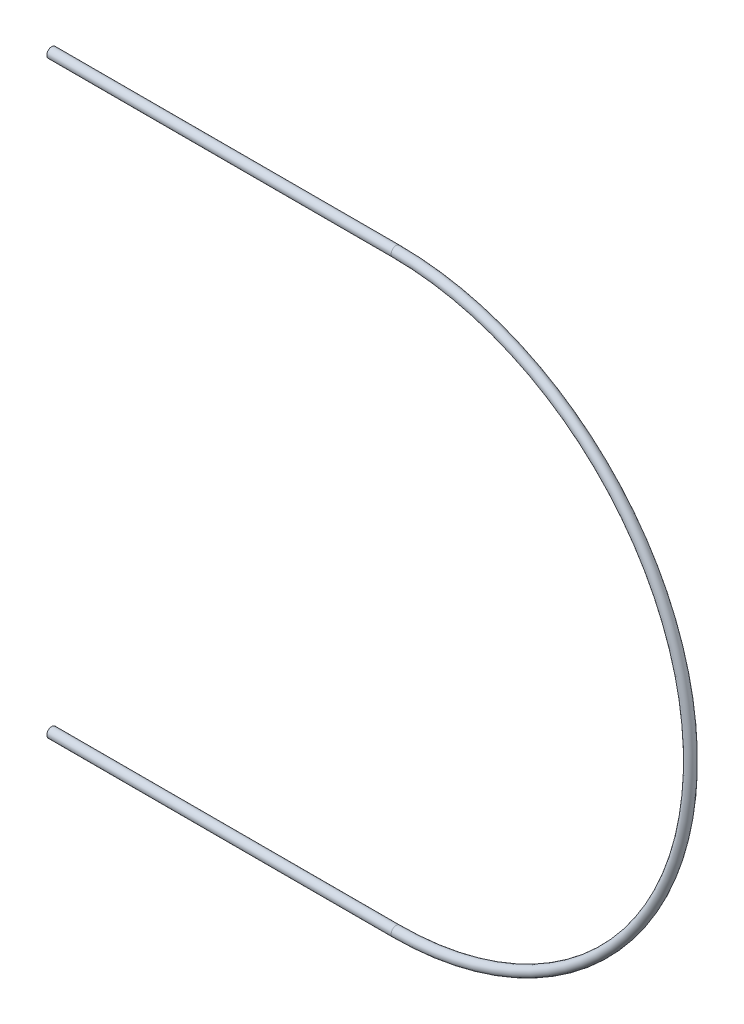
SolidWorks part; units mm, degrees
material "SA-193 B7"
ref_plane "Front Plane" through (0, 0, 0) normal (0, 0, 1) x (1, 0, 0)
ref_plane "Top Plane" through (0, 0, 0) normal (0, 1, 0) x (1, 0, 0)
ref_plane "Right Plane" through (0, 0, 0) normal (1, 0, 0) x (0, 0, -1)
sketch "Sketch1" plane through (0, 0, 0) normal (0, 0, 1) x (1, 0, 0)
  line B0 (-420, 359) -> (0, 359)
  line B1 (0, 0) -> (359, 0) construction
  line B2 (-420, -359) -> (0, -359)
  arc B3 (0, 359) -> (0, -359) centre (0, 0) cw
sketch_block_instance "U-bolt-2"
sketch_block "U-bolt" parameters "D2"=359, "D1"=420
sweep "Sweep1" add path "Sketch1" circular profile diameter 12 parameters "D3"=12
cosmetic thread "Cosmetic Thread1"
cosmetic thread "Cosmetic Thread2"
